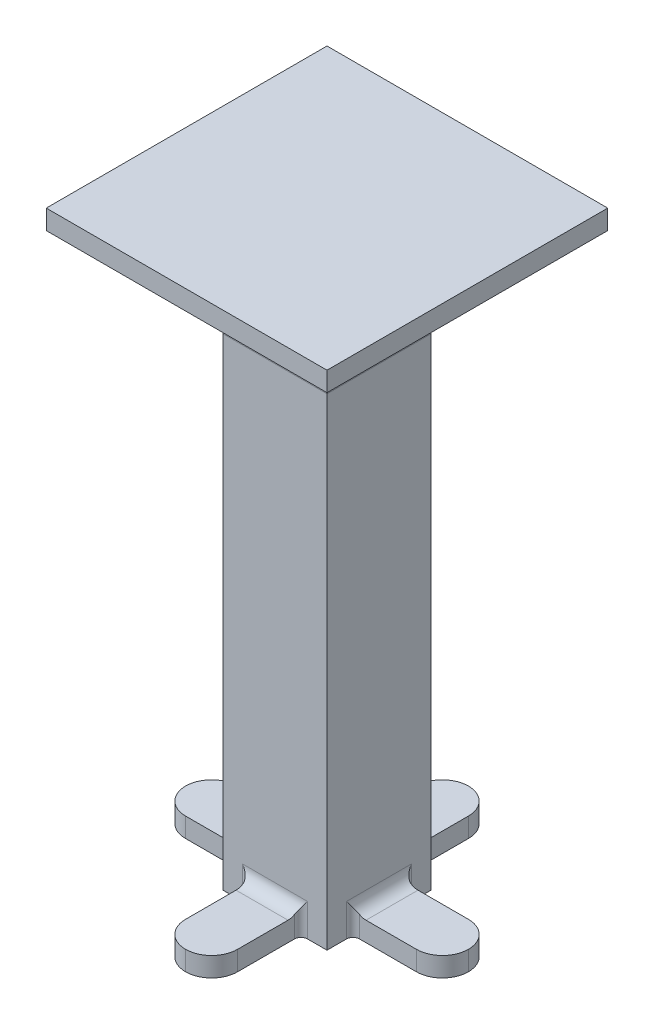
SolidWorks part; units mm, degrees
ref_plane "Front Plane" through (0, 0, 0) normal (0, 0, 1) x (1, 0, 0)
ref_plane "Top Plane" through (0, 0, 0) normal (0, 1, 0) x (1, 0, 0)
ref_plane "Right Plane" through (0, 0, 0) normal (1, 0, 0) x (0, 0, -1)
sketch "Sketch1" plane through (0, 0, 0) normal (0, 1, 0) x (1, 0, 0)
  line L1 (-6.35, -17.272) -> (6.35, -17.272)
  line L2 (-6.35, -17.272) -> (-6.35, 17.272)
  line L3 (-6.35, 17.272) -> (6.35, 17.272)
  line L4 (6.35, -17.272) -> (6.35, 17.272)
  line L5 (-6.35, -17.272) -> (6.35, 17.272) construction
  line L6 (-6.35, 17.272) -> (6.35, -17.272) construction
  line L7 (-17.272, -6.35) -> (17.272, -6.35)
  line L8 (-17.272, -6.35) -> (-17.272, 6.35)
  line L9 (-17.272, 6.35) -> (17.272, 6.35)
  line L10 (17.272, -6.35) -> (17.272, 6.35)
  line L11 (-17.272, -6.35) -> (17.272, 6.35) construction
  line L12 (-17.272, 6.35) -> (17.272, -6.35) construction
  point P0 (0, 0)
  point P6 (0, 0)
  dimension "D1" = 12.7
  dimension "D2" = 34.544
  dimension "D3" = 34.544
  dimension "D4" = 12.7
extrude "Boss-Extrude1" add sketch "Sketch1" along normal blind 2.3813 contours L9 L8 L7 L2 | L9 L2 L7 L4 | L2 L9 L4 L3 | L7 L10 L9 L4 | L7 L2 L1 L4 region at (0, 0, 11.811) region at (-11.811, 0, 0) region at (0, 0, 0) region at (11.811, 0, 0) region at (0, 0, -11.811)
sketch "Sketch2" plane through (0, 2.3813, 0) normal (0, 1, 0) x (1, 0, 0)
  line L1 (-6.35, -6.35) -> (6.35, -6.35)
  line L2 (-6.35, -6.35) -> (-6.35, 6.35)
  line L3 (-6.35, 6.35) -> (6.35, 6.35)
  line L4 (6.35, -6.35) -> (6.35, 6.35)
  line L5 (-6.35, -6.35) -> (6.35, 6.35) construction
  line L6 (-6.35, 6.35) -> (6.35, -6.35) construction
  point P0 (0, 0)
extrude "Boss-Extrude2" add sketch "Sketch2" along normal blind 67.3862
sketch "Sketch3" plane through (0, 69.7674, 0) normal (0, 1, 0) x (1, 0, 0)
  line L1 (-17.145, -17.145) -> (17.145, -17.145)
  line L2 (-17.145, -17.145) -> (-17.145, 17.145)
  line L3 (-17.145, 17.145) -> (17.145, 17.145)
  line L4 (17.145, -17.145) -> (17.145, 17.145)
  line L5 (-17.145, -17.145) -> (17.145, 17.145) construction
  line L6 (-17.145, 17.145) -> (17.145, -17.145) construction
  point P0 (0, 0)
  dimension "D1" = 34.29
  dimension "D2" = 34.29
extrude "Boss-Extrude3" add sketch "Sketch3" along normal blind 2.3813
fillet "Fillet15" radius 10.922 4 edges at (0, 69.7674, -6.35) (6.35, 69.7674, 0) (-6.35, 69.7674, 0) (0, 69.7674, 6.35)
sketch "Sketch4" plane through (0, 0, 0) normal (0, -1, 0) x (1, 0, 0)
  circle A0 centre (0, 0) radius 5.5562
  dimension "D1" = 11.1125
extrude "Cut-Extrude1" cut sketch "Sketch4" against normal blind 66.675 contours A0
sketch "Sketch5" plane through (0, 0, 0) normal (0, -1, 0) x (1, 0, 0)
  line L1 (-6.35, 6.35) -> (-3.175, 6.35)
  line L2 (-6.35, 6.35) -> (-6.35, 18.6009)
  line L3 (-6.35, 18.6009) -> (-3.175, 18.6009)
  line L4 (-3.175, 6.35) -> (-3.175, 18.6009)
  line L5 (6.35, 6.35) -> (3.175, 6.35)
  line L6 (6.35, 6.35) -> (6.35, 19.4213)
  line L7 (6.35, 19.4213) -> (3.175, 19.4213)
  line L8 (3.175, 6.35) -> (3.175, 19.4213)
  line L9 (6.35, 6.35) -> (22.2536, 6.35)
  line L10 (6.35, 6.35) -> (6.35, 3.175)
  line L11 (6.35, 3.175) -> (22.2536, 3.175)
  line L12 (22.2536, 6.35) -> (22.2536, 3.175)
  line L13 (6.35, -6.35) -> (23.7102, -6.35)
  line L14 (6.35, -6.35) -> (6.35, -3.175)
  line L15 (6.35, -3.175) -> (23.7102, -3.175)
  line L16 (23.7102, -6.35) -> (23.7102, -3.175)
  line L17 (6.35, -6.35) -> (3.175, -6.35)
  line L18 (6.35, -6.35) -> (6.35, -24.8431)
  line L19 (6.35, -24.8431) -> (3.175, -24.8431)
  line L20 (3.175, -6.35) -> (3.175, -24.8431)
  line L21 (-6.35, -6.35) -> (-3.175, -6.35)
  line L22 (-6.35, -6.35) -> (-6.35, -25.976)
  line L23 (-6.35, -25.976) -> (-3.175, -25.976)
  line L24 (-3.175, -6.35) -> (-3.175, -25.976)
  line L25 (-6.35, -6.35) -> (-27.5136, -6.35)
  line L26 (-6.35, -6.35) -> (-6.35, -3.175)
  line L27 (-6.35, -3.175) -> (-27.5136, -3.175)
  line L28 (-27.5136, -6.35) -> (-27.5136, -3.175)
  line L29 (-6.35, 6.35) -> (-27.5136, 6.35)
  line L30 (-6.35, 6.35) -> (-6.35, 3.175)
  line L31 (-6.35, 3.175) -> (-27.5136, 3.175)
  line L32 (-27.5136, 6.35) -> (-27.5136, 3.175)
  line M4 (17.272, 6.35) -> (6.35, 6.35)
  line M5 (6.35, 6.35) -> (6.35, 17.272)
  line M8 (-6.35, 17.272) -> (-6.35, 6.35)
  line M9 (-6.35, 6.35) -> (-17.272, 6.35)
  line M12 (-17.272, -6.35) -> (-6.35, -6.35)
  line M13 (-6.35, -6.35) -> (-6.35, -17.272)
  line M16 (6.35, -17.272) -> (6.35, -6.35)
  line M17 (6.35, -6.35) -> (17.272, -6.35)
  line M18 (-6.35, -17.272) -> (6.35, -17.272)
  line M19 (17.272, -6.35) -> (17.272, 6.35)
  line M20 (6.35, 17.272) -> (-6.35, 17.272)
  line M21 (-17.272, 6.35) -> (-17.272, -6.35)
  dimension "D1" = 3.175
  dimension "D2" = 3.175
  dimension "D3" = 3.175
  dimension "D4" = 3.175
  dimension "D5" = 3.175
  dimension "D6" = 3.175
  dimension "D7" = 3.175
  dimension "D8" = 3.175
extrude "Cut-Extrude2" cut sketch "Sketch5" against normal up to next contours L31 L30 M9 M21 | L1 L4 M20 M8 | L8 L5 M5 M20 | L10 L11 M19 M4 | L15 L14 M17 M19 | L17 L20 M18 M16 | L24 L21 M13 M18 | L26 L27 M21 M12 region at (-4.7625, 0, 11.811) region at (-11.811, 0, 4.7625) region at (4.7625, 0, 11.811) region at (-11.811, 0, -4.7625) region at (11.811, 0, 4.7625) region at (-4.7625, 0, -11.811) region at (11.811, 0, -4.7625) region at (4.7625, 0, -11.811)
fillet "Fillet18" radius 3.175 8 edges at (-17.272, 1.1906, 3.175) (-17.272, 1.1906, -3.175) (-3.175, 1.1906, -17.272) (3.175, 1.1906, -17.272) (17.272, 1.1906, -3.175) (17.272, 1.1906, 3.175) (-3.175, 1.1906, 17.272) (3.175, 1.1906, 17.272)
fillet "Fillet28" radius 0.7937 8 edges at (6.35, 1.1906, 3.175) (3.175, 1.1906, 6.35) (6.35, 1.1906, -3.175) (3.175, 1.1906, -6.35) (-3.175, 1.1906, -6.35) (-6.35, 1.1906, -3.175) (-6.35, 1.1906, 3.175) (-3.175, 1.1906, 6.35)
fillet "Fillet29" radius 1.5875 4 edges at (-6.35, 2.3813, 0) (0, 2.3813, -6.35) (0, 2.3813, 6.35) (6.35, 2.3813, 0)
